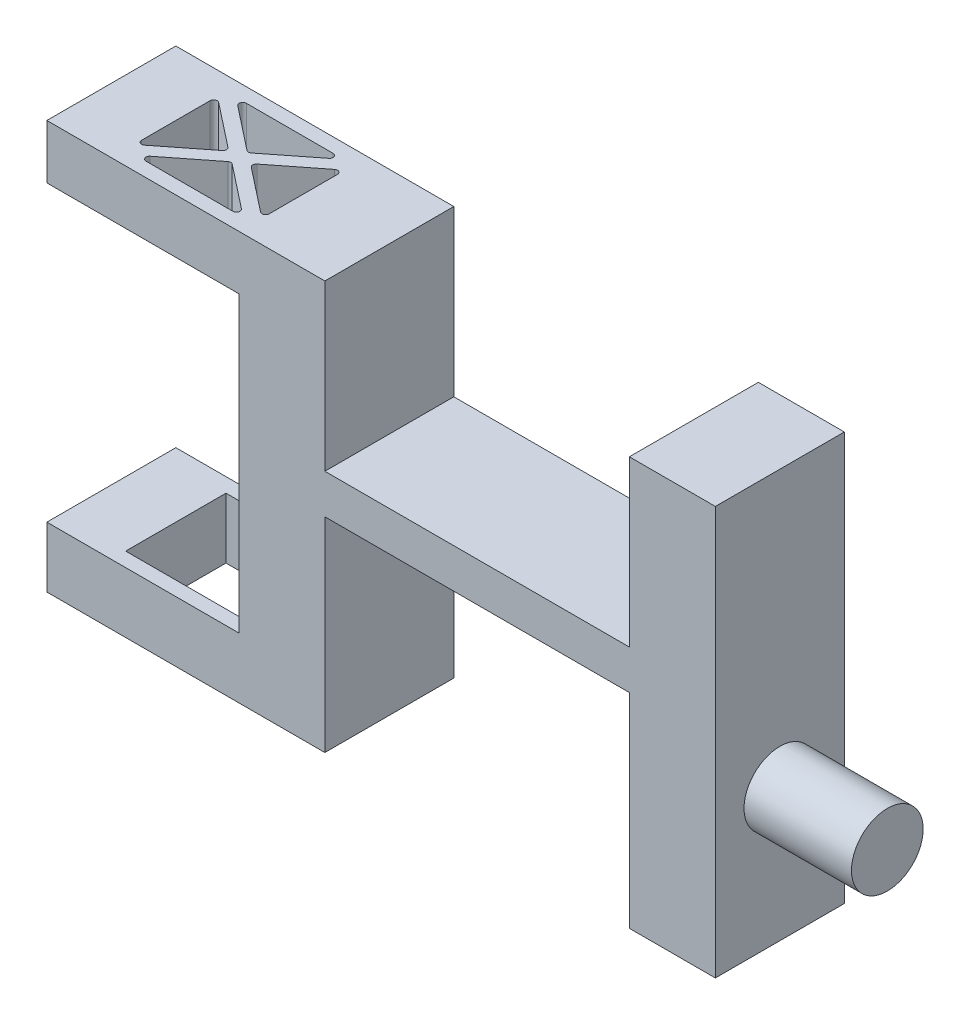
SolidWorks part; units mm, degrees
material "PLA"
ref_plane "Front Plane" through (0, 0, 0) normal (0, 0, 1) x (1, 0, 0)
ref_plane "Top Plane" through (0, 0, 0) normal (0, 1, 0) x (1, 0, 0)
ref_plane "Right Plane" through (0, 0, 0) normal (1, 0, 0) x (0, 0, -1)
sketch "Sketch2" plane through (0, 0, 0) normal (0, 0, 1) x (1, 0, 0)
  line L0 (0, -55) -> (0, 55) construction
  line L1 (0, 55) -> (66.5, 55)
  line L2 (0, 55) -> (0, 0)
  line L3 (0, 0) -> (66.5, 0)
  line L4 (66.5, 55) -> (66.5, 0)
  line L5 (55, 0) -> (-55, 0) construction
  line L7 (12, 50.75) -> (54.5, 50.75)
  line L8 (12, 50.75) -> (12, 30.25)
  line L9 (12, 30.25) -> (54.5, 30.25)
  line L10 (54.5, 50.75) -> (54.5, 30.25)
  line L11 (12, 24.75) -> (54.5, 24.75)
  line L12 (12, 24.75) -> (12, 4.25)
  line L13 (12, 4.25) -> (54.5, 4.25)
  line L14 (54.5, 24.75) -> (54.5, 4.25)
  dimension "D1" = 55
  dimension "D2" = 12
  dimension "D3" = 42.5
  dimension "D4" = 20.5
  dimension "D5" = 5.5
  dimension "D6" = 42.5
  dimension "D7" = 20.5
  dimension "D8" = 12
  dimension "D9" = 4.25
  dimension "D10" = 12
extrude "Boss-Extrude1" add sketch "Sketch2" along normal blind 18
sketch "Sketch3" plane through (0, 0, 18) normal (0, 0, 1) x (1, 0, 0)
  line L2 (12, 24.75) -> (12, 4.25) construction
  line L3 (54.5, 24.75) -> (12, 24.75) construction
  circle A8 centre (8.15, 19.75) radius 2.5
  circle A9 centre (8.15, 9.75) radius 2.5
  circle A10 centre (57.85, 9.75) radius 2.5
  circle A11 centre (57.85, 19.75) radius 2.5
  dimension "D9" = 45.85
  dimension "D10" = 45.85
  dimension "D11" = 5
  dimension "D12" = 5
  dimension "D13" = 3.85
  dimension "D14" = 3.85
  dimension "D15" = 10
  dimension "D16" = 5
  dimension "D17" = 5
  dimension "D18" = 5
  dimension "D19" = 5
  dimension "D24" = 10
sketch "Sketch5" plane through (0, 0, 0) normal (-1, 0, 0) x (0, 0, 1)
  line L0 (0, -55) -> (0, 55) construction
  line L1 (0, 55) -> (2, 55)
  line L2 (0, 55) -> (0, 49)
  line L3 (0, 49) -> (2, 49)
  line L4 (2, 55) -> (2, 49)
  line L5 (18, 55) -> (0, 55) construction
  line L6 (55, 0) -> (-55, 0) construction
  line L7 (18, 55) -> (16, 55)
  line L8 (18, 55) -> (18, 49)
  line L9 (18, 49) -> (16, 49)
  line L10 (16, 55) -> (16, 49)
  line L11 (0, 0) -> (2, 0)
  line L12 (0, 0) -> (0, 6)
  line L13 (0, 6) -> (2, 6)
  line L14 (2, 0) -> (2, 6)
  line L15 (18, 0) -> (16, 0)
  line L16 (18, 0) -> (18, 6)
  line L17 (18, 6) -> (16, 6)
  line L18 (16, 0) -> (16, 6)
  line L19 (18, 55) -> (18, 0) construction
  dimension "D1" = 2
  dimension "D2" = 2
  dimension "D3" = 6
  dimension "D4" = 6
  dimension "D5" = 2
  dimension "D6" = 2
  dimension "D7" = 6
  dimension "D8" = 6
extrude "Boss-Extrude2" add sketch "Sketch5" along normal blind 26.8
sketch "Sketch6" plane through (0, 0, 2) normal (0, 0, 1) x (1, 0, 0)
  line L0 (-26.8, 49) -> (0, 49) construction
  line L1 (-23.8, 49) -> (-26.8, 49)
  line L2 (-23.8, 49) -> (-23.8, 55)
  line L3 (-23.8, 55) -> (-26.8, 55)
  line L4 (-26.8, 49) -> (-26.8, 55)
  line L5 (66.5, 55) -> (-26.8, 55) construction
  line L6 (-26.8, 55) -> (-26.8, 49) construction
  line L7 (55, 0) -> (-55, 0) construction
  line L8 (-26.8, 6) -> (-24.8, 6)
  line L9 (-26.8, 6) -> (-26.8, 0)
  line L10 (-26.8, 0) -> (-24.8, 0)
  line L11 (-24.8, 6) -> (-24.8, 0)
  dimension "D1" = 3
  dimension "D2" = 2
extrude "Boss-Extrude3" add sketch "Sketch6" along normal up to next
sketch "Sketch8" plane through (0, 0, 18) normal (0, 0, 1) x (1, 0, 0)
  line L0 (66.5, 55) -> (-26.8, 55) construction
  line L1 (12, 50.75) -> (54, 50.75)
  line L2 (12, 50.75) -> (12, 55)
  line L3 (12, 55) -> (54, 55)
  line L4 (54, 50.75) -> (54, 55)
  line L5 (55, 0) -> (-55, 0) construction
  line L6 (12, 4.25) -> (54.5, 4.25)
  line L7 (12, 4.25) -> (12, 0)
  line L8 (12, 0) -> (54.5, 0)
  line L9 (54.5, 4.25) -> (54.5, 0)
extrude "Cut-Extrude3" cut sketch "Sketch8" against normal up to next
sketch "Sketch12" plane through (0, 0, 2) normal (0, 0, 1) x (1, 0, 0)
  line L0 (-26.8, 6) -> (0, 6) construction
  line L1 (-8, 6) -> (-5, 6)
  line L2 (-8, 6) -> (-8, 0)
  line L3 (-8, 0) -> (-5, 0)
  line L4 (-5, 6) -> (-5, 0)
  line L5 (55, 0) -> (-55, 0) construction
  line L6 (0, -55) -> (0, 55) construction
  dimension "D1" = 3
  dimension "D2" = 5
extrude "Boss-Extrude7" add sketch "Sketch12" along normal up to surface (14 mm away) up to face at (-12.4, 3, 16)
sketch "Sketch14" plane through (-8, 0, 0) normal (-1, 0, 0) x (0, 0, 1)
  line L0 (18, 6) -> (0, 6) construction
  line L1 (7, 6) -> (11, 6)
  line L2 (7, 6) -> (7, 0)
  line L3 (7, 0) -> (11, 0)
  line L4 (11, 6) -> (11, 0)
  line L5 (55, 0) -> (-55, 0) construction
  line L6 (0, -55) -> (0, 55) construction
  line L7 (18, 0) -> (18, 6) construction
  dimension "D1" = 7
  dimension "D2" = 7
extrude "Boss-Extrude8" add sketch "Sketch14" along normal up to surface (16.8 mm away) up to face at (-24.8, 3, 9)
sketch "Sketch17" plane through (0, 0, 2) normal (0, 0, 1) x (1, 0, 0)
  line L1 (-23.8, 55) -> (0, 55)
  line L2 (-23.8, 55) -> (-23.8, 49)
  line L3 (-23.8, 49) -> (0, 49)
  line L4 (0, 55) -> (0, 49)
extrude "Boss-Extrude9" add sketch "Sketch17" along normal blind 14 and the other way blind 1
sketch "Sketch18" plane through (0, 6, 0) normal (0, 1, 0) x (1, 0, 0)
  line L1 (-5, -2) -> (-24.8, -2)
  line L2 (-5, -2) -> (-5, -16)
  line L3 (-5, -16) -> (-24.8, -16)
  line L4 (-24.8, -2) -> (-24.8, -16)
extrude "Cut-Extrude4" cut sketch "Sketch18" against normal blind 10
sketch "Sketch20" plane through (0, 6, 0) normal (0, 1, 0) x (1, 0, 0)
  line L0 (-24.8, -16) -> (0, -16) construction
  line L1 (-24.8, -2) -> (-19.8, -2)
  line L2 (-24.8, -2) -> (-24.8, -16)
  line L3 (-24.8, -16) -> (-19.8, -16)
  line L4 (-19.8, -2) -> (-19.8, -16)
  dimension "D1" = 5
extrude "Boss-Extrude10" add sketch "Sketch20" against normal blind 6
sketch "Sketch22" plane through (0, 55, 0) normal (0, 1, 0) x (1, 0, 0)
  line L0 (-55, 0) -> (55, 0) construction
  line L1 (-26.8, -18) -> (12, -18)
  line L2 (-26.8, -18) -> (-26.8, 0)
  line L3 (-26.8, 0) -> (12, 0)
  line L4 (12, -18) -> (12, 0)
  line L5 (12, -18) -> (12, 0) construction
extrude "Boss-Extrude11" add sketch "Sketch22" along normal blind 1
sketch "Sketch23" plane through (0, 49, 0) normal (0, -1, 0) x (1, 0, 0)
  line L1 (0, 18) -> (-26.8, 18)
  line L2 (0, 18) -> (0, 0)
  line L3 (0, 0) -> (-26.8, 0)
  line L4 (-26.8, 18) -> (-26.8, 0)
extrude "Boss-Extrude12" add sketch "Sketch23" along normal blind 1
sketch "Sketch24" plane through (0, 6, 0) normal (0, 1, 0) x (1, 0, 0)
  line L0 (0, 0) -> (-26.8, 0)
  line L1 (-26.8, 0) -> (-26.8, -18)
  line L2 (-26.8, -18) -> (0, -18)
  line L3 (0, -18) -> (0, -16)
  line L4 (0, -16) -> (-19.8, -16)
  line L5 (-19.8, -16) -> (-19.8, -2)
  line L6 (-19.8, -2) -> (0, -2)
  line L7 (0, -2) -> (0, 0)
extrude "Boss-Extrude13" add sketch "Sketch24" along normal blind 1
sketch "Sketch25" plane through (0, 55, 0) normal (0, 1, 0) x (1, 0, 0)
  line L0 (-55, 0) -> (55, 0) construction
  line L1 (66.5, -18) -> (54.5, -18)
  line L2 (66.5, -18) -> (66.5, 0)
  line L3 (66.5, 0) -> (54.5, 0)
  line L4 (54.5, -18) -> (54.5, 0)
  line L5 (54.5, -18) -> (54.5, 0) construction
extrude "Boss-Extrude14" add sketch "Sketch25" along normal blind 1
sketch "Sketch27" plane through (0, 0, 0) normal (0, -1, 0) x (1, 0, 0)
  line L0 (-26.8, 18) -> (12, 18)
  line L1 (12, 18) -> (12, 0)
  line L2 (55, 0) -> (-55, 0) construction
  line L3 (12, 18) -> (12, 0) construction
  line L4 (12, 0) -> (-26.8, 0)
  line L5 (-26.8, 0) -> (-26.8, 18) construction
  line L6 (-26.8, 0) -> (-26.8, 18)
  line L7 (-19.8, 16) -> (-19.8, 2)
  line L8 (-19.8, 2) -> (0, 2)
  line L9 (0, 2) -> (0, 16)
  line L10 (0, 16) -> (0, 2) construction
  line L11 (-19.8, 16) -> (0, 16) construction
  line L12 (0, 16) -> (-19.8, 16)
extrude "Boss-Extrude15" add sketch "Sketch27" along normal blind 1
sketch "Sketch28" plane through (0, 0, 0) normal (0, -1, 0) x (1, 0, 0)
  line L0 (55, 0) -> (-55, 0) construction
  line L1 (54.5, 18) -> (66.5, 18)
  line L2 (54.5, 18) -> (54.5, 0)
  line L3 (54.5, 0) -> (66.5, 0)
  line L4 (66.5, 18) -> (66.5, 0)
  line L5 (66.5, 18) -> (66.5, 0) construction
extrude "Boss-Extrude16" add sketch "Sketch28" along normal blind 1
sketch "Sketch32" plane through (-26.8, 0, 0) normal (-1, 0, 0) x (0, 0, 1)
  line L0 (0, -55) -> (0, 55) construction
  line L1 (18, 7) -> (0, 7)
  line L2 (18, 7) -> (18, 4.25)
  line L3 (18, 4.25) -> (0, 4.25)
  line L4 (0, 7) -> (0, 4.25)
  dimension "D1" = 2.75
extrude "Cut-Extrude8" cut sketch "Sketch32" against normal blind 26.8
sketch "Sketch33" plane through (0, -1, 0) normal (0, -1, 0) x (1, 0, 0)
  line L0 (-26.8, 18) -> (12, 18)
  line L1 (12, 18) -> (12, 0)
  line L2 (31.35, 0) -> (-31.35, 0) construction
  line L3 (12, 18) -> (12, 0) construction
  line L4 (12, 0) -> (-26.8, 0)
  line L5 (-26.8, 18) -> (-26.8, 0) construction
  line L6 (-26.8, 0) -> (-26.8, 18)
  line L7 (-19.8, 16) -> (0, 16)
  line L8 (0, -9.9) -> (0, 9.9) construction
  line L9 (0, 16) -> (-19.8, 16) construction
  line L10 (0, 16) -> (0, 2)
  line L11 (0, 2) -> (-19.8, 2)
  line L12 (-19.8, 2) -> (-19.8, 16)
extrude "Boss-Extrude17" add sketch "Sketch33" along normal blind 2.75
sketch "Sketch34" plane through (0, -1, 0) normal (0, -1, 0) x (1, 0, 0)
  line L0 (31.35, 0) -> (-31.35, 0) construction
  line L1 (54.5, 18) -> (66.5, 18)
  line L2 (54.5, 18) -> (54.5, 0)
  line L3 (54.5, 0) -> (66.5, 0)
  line L4 (66.5, 18) -> (66.5, 0)
  line L5 (66.5, 0) -> (66.5, 18) construction
extrude "Boss-Extrude18" add sketch "Sketch34" along normal blind 2.75
sketch "Sketch35" plane through (0, 48, 0) normal (0, -1, 0) x (1, 0, 0)
  line L1 (-26.8, 18) -> (0, 18)
  line L2 (-26.8, 18) -> (-26.8, 0)
  line L3 (-26.8, 0) -> (0, 0)
  line L4 (0, 18) -> (0, 0)
extrude "Boss-Extrude19" add sketch "Sketch35" along normal blind 2.3
sketch "Sketch36" plane through (0, 56, 0) normal (0, 1, 0) x (1, 0, 0)
  line L0 (-31.35, 0) -> (31.35, 0) construction
  line L1 (66.5, -18) -> (54.5, -18)
  line L2 (66.5, -18) -> (66.5, 0)
  line L3 (66.5, 0) -> (54.5, 0)
  line L4 (54.5, -18) -> (54.5, 0)
  line L5 (54.5, -18) -> (54.5, 0) construction
  line L7 (12, -18) -> (-26.8, -18)
  line L8 (12, -18) -> (12, 0)
  line L9 (12, 0) -> (-26.8, 0)
  line L10 (-26.8, -18) -> (-26.8, 0)
extrude "Cut-Extrude9" cut sketch "Sketch36" against normal blind 2.75
sketch "Sketch37" plane through (-26.8, 0, 0) normal (-1, 0, 0) x (0, 0, 1)
  line L0 (0, 53.25) -> (18, 53.25) construction
  line L1 (0, -31.35) -> (0, 31.35) construction
  line L2 (18, 45.7) -> (18, 53.25) construction
  circle A0 centre (4, 49.45) radius 2.5
  circle A1 centre (14, 49.45) radius 2.5
  dimension "D1" = 3.8
  dimension "D2" = 4
  dimension "D3" = 4
  dimension "D4" = 3.8
  dimension "D5" = 5
  dimension "D6" = 5
sketch "Sketch38" plane through (-26.8, 0, 0) normal (-1, 0, 0) x (0, 0, 1)
  line L0 (0, 4.25) -> (18, 4.25) construction
  line L1 (0, -31.35) -> (0, 31.35) construction
  line L2 (18, -3.75) -> (18, 4.25) construction
  circle A0 centre (4, 0.45) radius 2.5
  circle A1 centre (14, 0.45) radius 2.5
  dimension "D1" = 3.8
  dimension "D2" = 5
  dimension "D3" = 4
  dimension "D4" = 5
  dimension "D5" = 4
  dimension "D6" = 3.8
extrude "Cut-Extrude10" cut sketch "Sketch37" against normal blind 6
sketch "Sketch39" plane through (0, 0, 0) normal (0, 0, -1) x (-1, 0, 0)
  line L0 (-54.5, 30.25) -> (-54.5, 27.5) construction
  line L2 (-54.5, 27.5) -> (-66.5, 27.5) construction
  line L3 (-66.5, -3.75) -> (-66.5, 53.25) construction
  circle A2 centre (-8.15, 19.75) radius 2.5
  circle A3 centre (-8.15, 9.75) radius 2.5
  circle A6 centre (-57.85, 19.75) radius 2.5
  circle A7 centre (-57.85, 9.75) radius 2.5
  circle A8 centre (-8.15, 45.25) radius 2.5
  circle A9 centre (-8.15, 35.25) radius 2.5
  circle A10 centre (-57.85, 45.25) radius 2.5
  circle A11 centre (-57.85, 35.25) radius 2.5
  dimension "D1" = 2.75
  dimension "D4" = 5
  dimension "D5" = 5
  dimension "D6" = 5
  dimension "D7" = 5
extrude "Cut-Extrude12" cut sketch "Sketch39" against normal blind 10
extrude "Cut-Extrude11" cut sketch "Sketch38" against normal blind 6
sketch "Sketch40" plane through (0, 0, 0) normal (0, 0, -1) x (-1, 0, 0)
  line L0 (-57.85, 35.25) -> (-8.15, 35.25) construction
  line L1 (-57.85, 19.75) -> (-8.15, 19.75) construction
  line L3 (-54, 50.75) -> (-54.5, 50.75)
  line L4 (-54, 50.75) -> (-54, 55)
  line L5 (-54, 55) -> (-54.5, 55)
  line L6 (-54.5, 50.75) -> (-54.5, 55)
extrude "Cut-Extrude13" cut sketch "Sketch40" against normal up to surface (18 mm away) up to face at (25.44, 30.97, 18)
sketch "Sketch43" plane through (0, 4.25, 0) normal (0, 1, 0) x (1, 0, 0)
  line L0 (0, 0) -> (-26.8, 0)
  line L1 (-26.8, 0) -> (-26.8, -18)
  line L2 (-26.8, -18) -> (0, -18)
  line L3 (0, -18) -> (0, -16)
  line L4 (0, -16) -> (-19.8, -16)
  line L5 (-19.8, -16) -> (-19.8, -2)
  line L6 (-19.8, -2) -> (0, -2)
  line L7 (0, -2) -> (0, 0)
extrude "Boss-Extrude21" add sketch "Sketch43" along normal blind 0.45
sketch "Sketch44" plane through (66.5, 0, 0) normal (1, 0, 0) x (0, 0, -1)
  line L0 (0, -3.75) -> (-18, -3.75) construction
  line L1 (-18, -3.75) -> (-18, 53.25) construction
  circle A0 centre (-9, 14.75) radius 5
  dimension "D1" = 10
  dimension "D2" = 18.5
  dimension "D3" = 9
extrude "Boss-Extrude22" add sketch "Sketch44" along normal blind 15
sketch "Sketch45" plane through (-19.8, 0, 0) normal (1, 0, 0) x (0, 0, -1)
  line L1 (-16, 4.7) -> (-2, 4.7)
  line L2 (-16, 4.7) -> (-16, -3.75)
  line L3 (-16, -3.75) -> (-2, -3.75)
  line L4 (-2, 4.7) -> (-2, -3.75)
  line L5 (-16, 4.7) -> (-2, -3.75) construction
  line L6 (-16, -3.75) -> (-2, 4.7) construction
  point P4 (-9, 0.475)
extrude "Boss-Extrude23" add sketch "Sketch45" along normal blind 2
sketch "Sketch48" plane through (0, 45.7, 0) normal (0, -1, 0) x (-1, 0, 0)
  line L0 (17.8, -16) -> (0, -2) construction
  line L1 (17.8, -16) -> (0, -16) construction
  line L2 (17.8, -16) -> (17.8, -2) construction
  line L3 (17.8, -2) -> (0, -2) construction
  line L4 (0, -16) -> (0, -2) construction
  line L5 (0, -16) -> (17.8, -2) construction
  line L6 (8.9, -16) -> (8.9, -2) construction
  line L7 (17.8, -9) -> (0, -9) construction
  line L8 (8.9, -16) -> (1.4, -16)
  line L9 (1.4, -16) -> (8.9, -10.1012)
  line L10 (8.9, -10.1012) -> (16.4, -16)
  line L11 (16.4, -16) -> (8.9, -16)
  line L12 (1.3986, -2) -> (8.9, -7.9)
  line L13 (8.9, -7.9) -> (16.4014, -2)
  line L14 (16.4014, -2) -> (1.3986, -2)
  line L15 (0, -9) -> (0, -3.2)
  line L16 (0, -3.2) -> (7.3743, -9)
  line L17 (7.3743, -9) -> (0, -14.8)
  line L18 (0, -14.8) -> (0, -3.2)
  line L19 (17.8, -3.1959) -> (10.4205, -9)
  line L20 (10.4205, -9) -> (17.8, -14.8041)
  line L21 (17.8, -14.8041) -> (17.8, -3.1959)
  point P15 (8.9, -9)
  dimension "D1" = 7.5
  dimension "D2" = 7.5
  dimension "D3" = 1.1
  dimension "D4" = 5.8
  dimension "D5" = 0.94
extrude "Cut-Extrude14" cut sketch "Sketch48" against normal through all contours L14 L12 L13 | L16 L17 L18 | L21 L19 L20 | L11 L8 L9 L10
fillet "Fillet1" radius 0.5 12 edges at (-1.3986, 49.475, 2) (-16.4014, 49.475, 2) (-17.8, 49.475, 3.1959) (-10.4205, 49.475, 9) (-17.8, 49.475, 14.8041) (-16.4, 49.475, 16) (-1.4, 49.475, 16) (-8.9, 49.475, 10.1012) (-7.3743, 49.475, 9) (0, 49.475, 3.2) (0, 49.475, 14.8) (-8.9, 49.475, 7.9)
